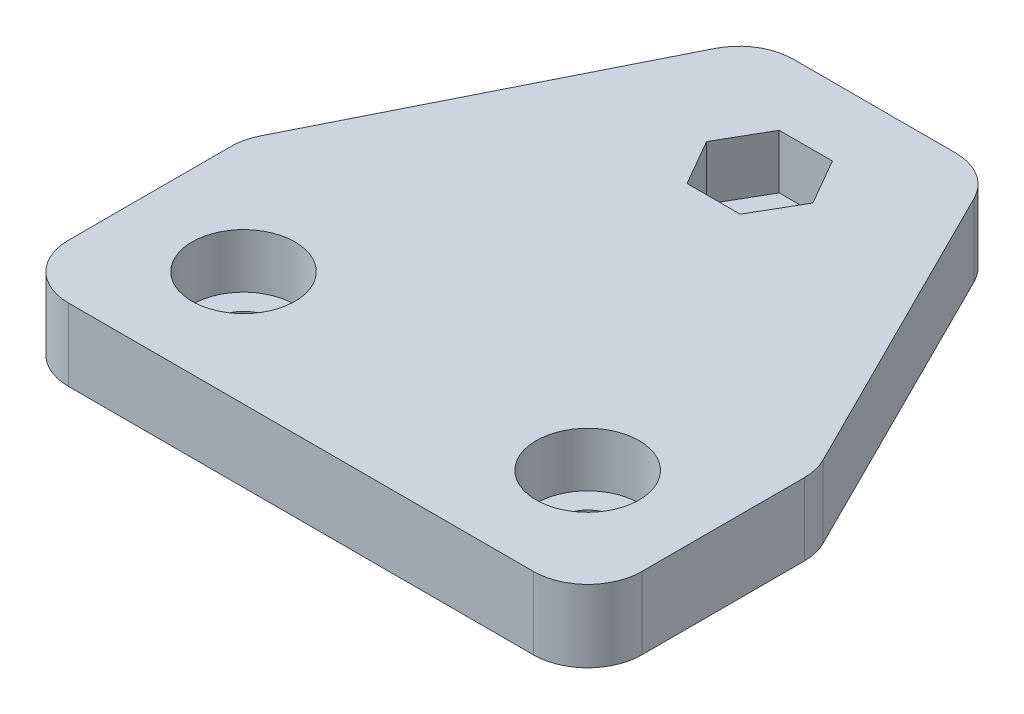
SolidWorks part; units mm, degrees
ref_plane "Front Plane" through (0, 0, 0) normal (0, 0, 1) x (1, 0, 0)
ref_plane "Top Plane" through (0, 0, 0) normal (0, 1, 0) x (1, 0, 0)
ref_plane "Right Plane" through (0, 0, 0) normal (1, 0, 0) x (0, 0, -1)
sketch "Sketch1" plane through (0, 0, 0) normal (0, 1, 0) x (1, 0, 0)
  line L0 (-31.75, 0) -> (31.75, 0)
  line L1 (-31.75, 0) -> (-31.75, 25.4)
  line L2 (-31.75, 25.4) -> (-12.7, 63.5)
  line L3 (-12.7, 63.5) -> (12.7, 63.5)
  line L4 (12.7, 63.5) -> (31.75, 25.4)
  line L5 (31.75, 25.4) -> (31.75, 0)
  point P0 (0, 63.5)
  point P4 (0, 0)
  point P10 (-11.4986, 63.5)
  point P11 (36.7901, 25.4)
  dimension "D1" = 25.4
  dimension "D2" = 63.5
  dimension "D3" = 25.4
  dimension "D4" = 63.5
extrude "Boss-Extrude1" add sketch "Sketch1" along normal blind 8
sketch "Sketch2" plane through (0, 8, 0) normal (0, 1, 0) x (1, 0, 0)
  line L0 (-31.75, 12.7) -> (0, 12.7) construction
  line L3 (0, 0) -> (0, 63.5) construction
  line L4 (12.7, 63.5) -> (-12.7, 63.5) construction
  line L5 (-31.75, 25.4) -> (-31.75, 0) construction
  line L6 (0, 12.7) -> (31.75, 12.7) construction
  line L7 (31.75, 0) -> (31.75, 25.4) construction
  circle A2 centre (0, 50.8) radius 3.1
  circle A3 centre (-19.05, 12.7) radius 3.1
  circle A4 centre (19.05, 12.7) radius 3.1
  dimension "D4" = 6.2
  dimension "D1" = 12.7
  dimension "D2" = 12.7
  dimension "D3" = 12.7
extrude "Cut-Extrude1" cut sketch "Sketch2" against normal through all both and the other way through all
fillet "Fillet1" radius 6 6 edges at (-12.7, 4, -63.5) (12.7, 4, -63.5) (31.75, 4, -25.4) (31.75, 4, 0) (-31.75, 4, 0) (-31.75, 4, -25.4)
sketch "Sketch3" plane through (0, 8, 0) normal (0, 1, 0) x (1, 0, 0)
  line L19 (5.889, 50.8) -> (2.9445, 55.9)
  line L20 (2.9445, 55.9) -> (-2.9445, 55.9)
  line L21 (-2.9445, 55.9) -> (-5.889, 50.8)
  line L22 (-5.889, 50.8) -> (-2.9445, 45.7)
  line L23 (-2.9445, 45.7) -> (2.9445, 45.7)
  line L24 (2.9445, 45.7) -> (5.889, 50.8)
  circle A0 centre (0, 50.8) radius 5.1 construction
  circle A1 centre (-19.05, 12.7) radius 5.7
  circle A2 centre (19.05, 12.7) radius 5.7
  dimension "D1" = 10.2
  dimension "D2" = 11.4
extrude "Cut-Extrude2" cut sketch "Sketch3" against normal blind 6 and the other way through all
